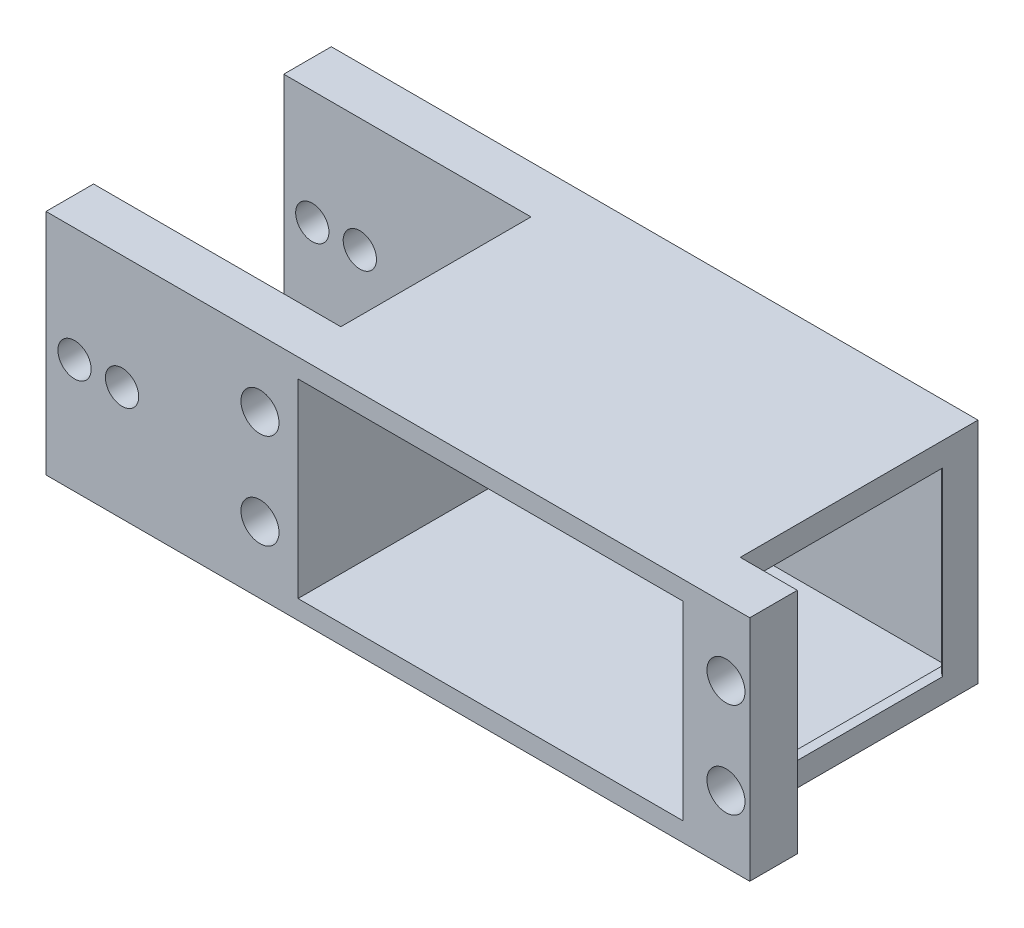
SolidWorks part; units mm, degrees
material "ABS"
ref_plane "Front Plane" through (0, 0, 0) normal (0, 0, 1) x (1, 0, 0)
ref_plane "Top Plane" through (0, 0, 0) normal (0, 1, 0) x (1, 0, 0)
ref_plane "Right Plane" through (0, 0, 0) normal (1, 0, 0) x (0, 0, -1)
sketch "Sketch1" plane through (0, 0, 0) normal (0, 0, 1) x (1, 0, 0)
  line L1 (-28, -12) -> (28, -12)
  line L2 (-28, -12) -> (-28, 12)
  line L3 (-28, 12) -> (28, 12)
  line L4 (28, -12) -> (28, 12)
  line L5 (-28, -12) -> (28, 12) construction
  line L6 (-28, 12) -> (28, -12) construction
  point P0 (0, 0)
  dimension "D1" = 56
  dimension "D2" = 24
extrude "Boss-Extrude1" add sketch "Sketch1" along normal blind 30
shell "Shell1" thickness 2 removed face at (0, 0, 30)
sketch "Sketch12" plane through (28, 0, 0) normal (1, 0, 0) x (0, 0, -1)
  line L0 (-30, -12) -> (0, -12) construction
  line L1 (-24, 9.5) -> (-4, 9.5)
  line L2 (-24, 9.5) -> (-24, -9.5)
  line L3 (-24, -9.5) -> (-4, -9.5)
  line L4 (-4, 9.5) -> (-4, -9.5)
  line L5 (-24, 9.5) -> (-4, -9.5) construction
  line L6 (-24, -9.5) -> (-4, 9.5) construction
  point P0 (-14, 0)
  dimension "D1" = 14
  dimension "D2" = 20
  dimension "D3" = 19
  dimension "D4" = 2.5
extrude "Cut-Extrude1" cut sketch "Sketch12" against normal blind 10
fillet "Fillet1" radius 2 1 edges at (21, 0, 4)
sketch "Sketch13" plane through (0, 0, 30) normal (0, 0, 1) x (1, 0, 0)
  line L0 (-28, 12) -> (-28, -12)
  line L1 (-28, -12) -> (-26, -12)
  line L2 (-28, -12) -> (28, -12) construction
  line L3 (-26, -12) -> (-26, 12)
  line L4 (28, 12) -> (-28, 12) construction
  line L5 (-26, 12) -> (-28, 12)
extrude "Cut-Extrude2" cut sketch "Sketch13" against normal through all
sketch "Sketch17" plane through (28, 0, 0) normal (1, 0, 0) x (0, 0, -1)
  line L1 (0, -12) -> (0, 12) construction
  line L2 (-25, -12) -> (-25, 12)
  line L3 (-30, -12) -> (0, -12) construction
  line L4 (-30, 12) -> (0, 12) construction
  line L5 (-25, 12) -> (0, 12)
  line L6 (0, 12) -> (0, -12)
  line L7 (0, -12) -> (-25, -12)
  point P11 (0, 0)
  dimension "D1" = 24
  dimension "D2" = 25
extrude "Cut-Extrude4" cut sketch "Sketch17" against normal blind 4
sketch "Sketch19" plane through (0, 0, 30) normal (0, 0, 1) x (1, 0, 0)
  circle A0 centre (-23.5, -5) radius 2
  circle A1 centre (-23.5, 5) radius 2
  circle A2 centre (25.5, 5) radius 2
  circle A3 centre (25.5, -5) radius 2
extrude "Cut-Extrude5" cut sketch "Sketch19" against normal blind 13
sketch "Sketch20" plane through (24, 0, 0) normal (1, 0, 0) x (0, 0, -1)
  line L0 (-25, 6.3229) -> (-25, 12)
  line L1 (-25, 12) -> (0, 12)
  line L2 (0, 12) -> (0, -12)
  line L3 (0, -12) -> (-25, -12)
  line L4 (-25, -12) -> (-25, -6.3229)
  line L6 (-24, -6.3229) -> (-24, -9.5)
  line L7 (-24, -9.5) -> (-4, -9.5)
  line L8 (-4, -9.5) -> (-4, 9.5)
  line L9 (-4, 9.5) -> (-24, 9.5)
  line L11 (-24, 9.5) -> (-24, 6.3229)
  line L13 (-24, 6.3229) -> (-24, -6.3229)
  line L14 (-25, 6.3229) -> (-25, -6.3229)
extrude "Cut-Extrude7" cut sketch "Sketch20" against normal blind 2
sketch "Sketch21" plane through (-26, 0, 0) normal (-1, 0, 0) x (0, 0, 1)
  line L0 (0, -12) -> (0, 12)
  line L1 (0, 12) -> (25, 12)
  line L2 (0, 12) -> (30, 12) construction
  line L3 (25, 12) -> (25, -12)
  line L4 (0, -12) -> (30, -12) construction
  line L5 (25, -12) -> (0, -12)
  line L6 (30, -12) -> (30, 12) construction
  dimension "D1" = 5
extrude "Cut-Extrude8" cut sketch "Sketch21" against normal blind 6
sketch "Sketch26" plane through (-26, 0, 0) normal (-1, 0, 0) x (0, 0, 1)
  line L0 (25, 12) -> (30, 12)
  line L1 (30, 12) -> (30, -12)
  line L2 (30, -12) -> (25, -12)
  line L3 (25, -12) -> (25, 12)
  dimension "D1" = 5
extrude "Boss-Extrude3" add sketch "Sketch26" along normal blind 20
sketch "Sketch27" plane through (-20, 0, 0) normal (-1, 0, 0) x (0, 0, 1)
  line L0 (0, 12) -> (0, -12)
  line L1 (0, -12) -> (5, -12)
  line L2 (0, -12) -> (25, -12) construction
  line L3 (5, -12) -> (5, 12)
  line L4 (25, 12) -> (0, 12) construction
  line L5 (5, 12) -> (0, 12)
extrude "Boss-Extrude4" add sketch "Sketch27" along normal blind 26
sketch "Sketch28" plane through (0, 0, 30) normal (0, 0, 1) x (1, 0, 0)
  line L0 (-46, -12) -> (-46, 12) construction
  line L1 (-46, -12) -> (28, -12) construction
  circle A0 centre (-43, 0) radius 1.75
  circle A1 centre (-38, 0) radius 1.75
  dimension "D1" = 5
  dimension "D2" = 3.5
  dimension "D3" = 3
  dimension "D4" = 12
  dimension "D5" = 12
extrude "Cut-Extrude9" cut sketch "Sketch28" against normal through all
